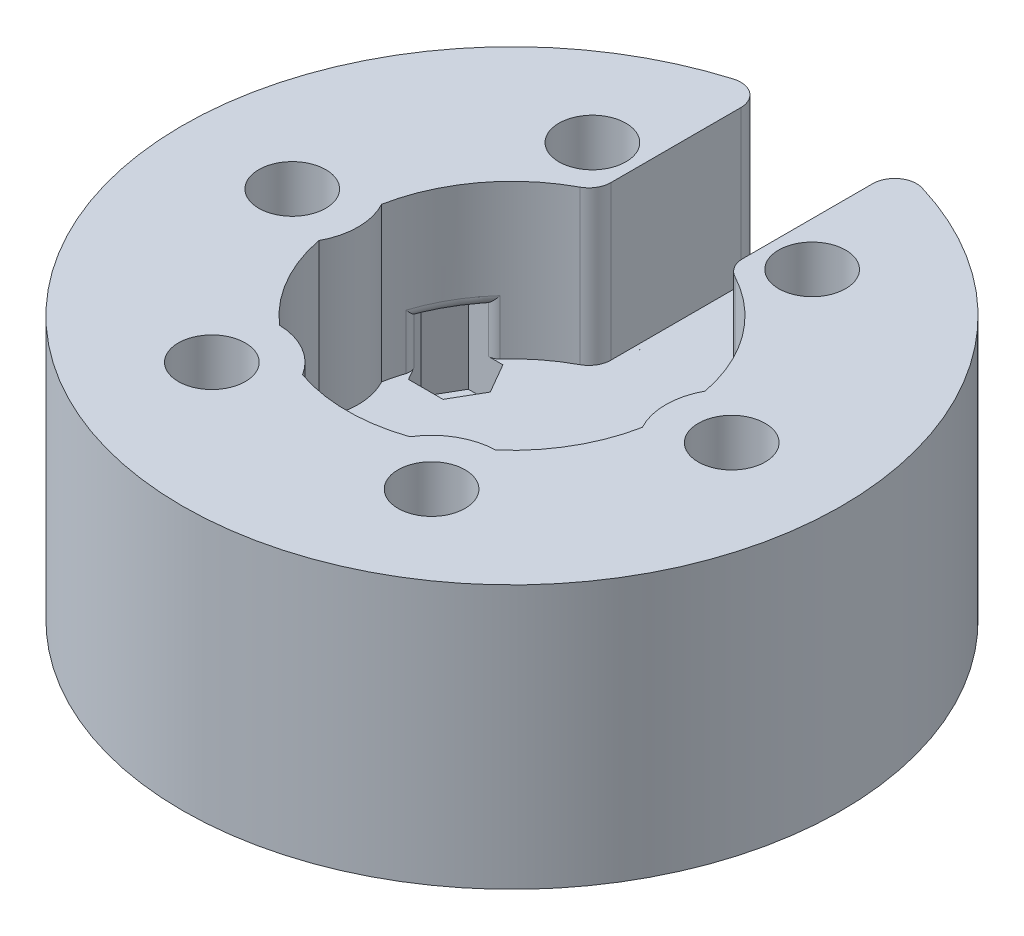
SolidWorks part; units mm, degrees
ref_plane "前视基准面" through (0, 0, 0) normal (0, 0, 1) x (1, 0, 0)
ref_plane "上视基准面" through (0, 0, 0) normal (0, 1, 0) x (1, 0, 0)
ref_plane "右视基准面" through (0, 0, 0) normal (1, 0, 0) x (0, 0, -1)
other "Configuration Table"
sketch "草图1" plane through (0, 0, 0) normal (0, 1, 0) x (1, 0, 0)
  line L0 (-30, 0) -> (30, 0) construction
  line L1 (-6, 0) -> (-3, -5.1962)
  line L2 (-3, -5.1962) -> (3, -5.1962)
  line L3 (3, -5.1962) -> (6, 0)
  line L4 (6, 0) -> (3, 5.1962)
  line L5 (3, 5.1962) -> (-3, 5.1962)
  line L6 (-3, 5.1962) -> (-6, 0)
  line L7 (0, 0) -> (-10, 17.3205) construction
  line L8 (-12.1244, 7) -> (0, 0) construction
  circle A0 centre (0, 0) radius 30
  circle A1 centre (0, 0) radius 5.1962 construction
  circle A2 centre (-10, 17.3205) radius 5.05
  circle A3 centre (10, 17.3205) radius 5.05
  circle A4 centre (20, 0) radius 5.05
  circle A5 centre (10, -17.3205) radius 5.05
  circle A6 centre (-10, -17.3205) radius 5.05
  circle A7 centre (-20, 0) radius 5.05
  circle A8 centre (-10, 17.3205) radius 3.05
  circle A9 centre (10, 17.3205) radius 3.05
  circle A10 centre (20, 0) radius 3.05
  circle A11 centre (10, -17.3205) radius 3.05
  circle A12 centre (-10, -17.3205) radius 3.05
  circle A13 centre (-20, 0) radius 3.05
  circle A14 centre (-12.1244, 7) radius 1.55
  circle A15 centre (12.1244, 7) radius 1.55
  circle A16 centre (0, -14) radius 1.55
  point P26 (0, 0)
  point P38 (0, 0)
  point P39 (4.8677, -12.6024)
  point P40 (0, 0)
  point P44 (0, 0)
  dimension "D1" = 60
  dimension "D3" = 10.1
  dimension "D7" = 6.1
  dimension "D10" = 3.1
  dimension "D2" = 6
  dimension "D4" = 20
  dimension "D5" = 60
  dimension "D9" = 120
  dimension "D11" = 14
  dimension "D12" = 150
  dimension "D6" = 6
  dimension "D8" = 6
  dimension "D13" = 3
extrude "凸台-拉伸3" add sketch "草图1" along normal blind 24 contours A0 A16 A15 A14 A7 A6 A5 A4 A3 A2 L6 L5 L4 L3 L2 L1 | A5 A11 | A4 A10 | A3 A9 | A6 A12 | A7 A13 | A2 A8 | A15 | A14 | A16 region at (-29.1515, 0, 0) region at (-14.9072, 0, -17.3205) region at (5.0928, 0, -17.3205) region at (15.0928, 0, 0) region at (5.0928, 0, 17.3205) region at (-14.9072, 0, 17.3205) region at (-24.9072, 0, 0) region at (-12.1244, 0, -7) region at (12.1244, 0, -7) region at (0, 0, 14)
sketch "草图3" plane through (0, 0, 0) normal (0, -1, 0) x (1, 0, 0)
  line L0 (6, 0) -> (3, -5.1962) construction
  line L1 (3, 5.1962) -> (6, 0) construction
  line L2 (-3, 5.1962) -> (3, 5.1962) construction
  line L3 (-6, 0) -> (-3, 5.1962) construction
  line L4 (-3, -5.1962) -> (-6, 0) construction
  line L5 (3, -5.1962) -> (-3, -5.1962) construction
  line L6 (6, 0) -> (3, -5.1962)
  line L7 (3, 5.1962) -> (6, 0)
  line L8 (-3, 5.1962) -> (3, 5.1962)
  line L9 (-6, 0) -> (-3, 5.1962)
  line L10 (-3, -5.1962) -> (-6, 0)
  line L11 (3, -5.1962) -> (-3, -5.1962)
  circle A0 centre (-20, 0) radius 3.05 construction
  circle A1 centre (-10, 17.3205) radius 3.05 construction
  circle A3 centre (10, 17.3205) radius 3.05 construction
  circle A4 centre (20, 0) radius 3.05 construction
  circle A5 centre (10, -17.3205) radius 3.05 construction
  circle A8 centre (-10, -17.3205) radius 3.05 construction
  circle A9 centre (0, 0) radius 30 construction
  circle A10 centre (-20, 0) radius 3.05
  circle A11 centre (-10, 17.3205) radius 3.05
  circle A13 centre (10, 17.3205) radius 3.05
  circle A14 centre (20, 0) radius 3.05
  circle A15 centre (10, -17.3205) radius 3.05
  circle A18 centre (-10, -17.3205) radius 3.05
  circle A19 centre (0, 0) radius 30
  circle A20 centre (-10, -17.3205) radius 5.05
  circle A21 centre (-20, 0) radius 5.05
  circle A22 centre (-10, 17.3205) radius 5.05
  circle A23 centre (10, 17.3205) radius 5.05
  circle A24 centre (20, 0) radius 5.05
  circle A25 centre (10, -17.3205) radius 5.05
  point P10 (0, 0)
  point P37 (0, 0)
  point P38 (10, -17.3205)
  point P50 (0, 0)
  circle M26 centre (-10, -17.3205) radius 3.05
  circle M27 centre (10, -17.3205) radius 3.05
  circle M28 centre (20, 0) radius 3.05
  circle M29 centre (10, 17.3205) radius 3.05
  circle M30 centre (-10, 17.3205) radius 3.05
  circle M31 centre (-20, 0) radius 3.05
  dimension "D1" = 10.1
  dimension "D2" = 6
extrude "切除-拉伸1" cut sketch "草图3" against normal blind 6 contours A24 M28 | A23 M29 | A22 M30 | A21 M31 | A20 M26 | A25 M27 region at (-14.9072, 0, -17.3205) region at (-24.9072, 0, 0) region at (-14.9072, 0, 17.3205) region at (5.0928, 0, 17.3205) region at (15.0928, 0, 0) region at (5.0928, 0, -17.3205)
sketch "草图5" plane through (0, 0, 0) normal (0, -1, 0) x (1, 0, 0)
  line L0 (-6, 0) -> (-3, 5.1962) construction
  line L1 (-3, -5.1962) -> (-6, 0) construction
  line L2 (3, -5.1962) -> (-3, -5.1962) construction
  line L3 (6, 0) -> (3, -5.1962) construction
  line L4 (3, 5.1962) -> (6, 0) construction
  line L5 (-3, 5.1962) -> (3, 5.1962) construction
  line L6 (-6, 0) -> (-3, 5.1962)
  line L7 (-3, -5.1962) -> (-6, 0)
  line L8 (3, -5.1962) -> (-3, -5.1962)
  line L9 (6, 0) -> (3, -5.1962)
  line L10 (3, 5.1962) -> (6, 0)
  line L11 (-3, 5.1962) -> (3, 5.1962)
extrude "凸台-拉伸4" add sketch "草图5" against normal blind 2 from offset 9 offset against normal yes
sketch "草图8" plane through (0, 24, 0) normal (0, 1, 0) x (1, 0, 0)
  line L0 (10, 17.3205) -> (-10, 17.3205) construction
  line L2 (-6, 2.3205) -> (6, 2.3205)
  line L3 (-6, 2.3205) -> (-6, 32.3205)
  line L4 (-6, 32.3205) -> (6, 32.3205)
  line L5 (6, 2.3205) -> (6, 32.3205)
  line L6 (-6, 2.3205) -> (6, 32.3205) construction
  line L7 (-6, 32.3205) -> (6, 2.3205) construction
  circle A0 centre (0, 0) radius 15
  circle A1 centre (0, 0) radius 30 construction
  circle A2 centre (10, 17.3205) radius 3.05 construction
  circle A3 centre (-10, 17.3205) radius 3.05 construction
  circle A4 centre (0, 0) radius 30
  circle A5 centre (10, 17.3205) radius 3.05
  circle A6 centre (-10, 17.3205) radius 3.05
  circle A7 centre (-20, 0) radius 3.05 construction
  circle A8 centre (-10, -17.3205) radius 3.05 construction
  circle A9 centre (10, -17.3205) radius 3.05 construction
  circle A10 centre (20, 0) radius 3.05 construction
  circle A11 centre (-20, 0) radius 3.05
  circle A12 centre (-10, -17.3205) radius 3.05
  circle A13 centre (10, -17.3205) radius 3.05
  circle A14 centre (20, 0) radius 3.05
  circle A15 centre (-20, 0) radius 6
  circle A16 centre (-10, -17.3205) radius 6
  circle A17 centre (10, -17.3205) radius 6
  circle A18 centre (20, 0) radius 6
  point P11 (0, 17.3205)
  point P29 (0, 0)
  point P30 (0, 0)
  point P32 (0, 0)
  point P36 (0, 0)
  line M13 (-6, 0) -> (-3, 5.1962)
  line M14 (-3, 5.1962) -> (3, 5.1962)
  line M15 (3, 5.1962) -> (6, 0)
  line M16 (6, 0) -> (3, -5.1962)
  line M17 (3, -5.1962) -> (-3, -5.1962)
  line M18 (-3, -5.1962) -> (-6, 0)
  circle M19 centre (0, 0) radius 30
  dimension "D1" = 30
  dimension "D4" = 12
  dimension "D2" = 12
  dimension "D3" = 30
  dimension "D5" = 4
extrude "切除-拉伸5" cut sketch "草图8" against normal blind 14 contours L3 A0 L5 L2 M15 M16 M17 M18 M13 | L2 M13 M18 M17 M16 M15 | L2 M13 M15 M14 | L5 A0 L3 L2 M13 M14 M15 | A0 L5 L3 M19 region at (0, 24, -9.3064) region at (-5.3301, 24, -1.909) region at (0, 24, -3.6545) region at (0, 24, 1.1258) region at (0, 24, -22.1908)
sketch "草图10" plane through (0, 0, 0) normal (0, -1, 0) x (1, 0, 0)
  line L0 (0, 0) -> (-30, 0) construction
  line L1 (0, 14) -> (0, 0)
  circle A0 centre (0, 0) radius 30 construction
  circle A1 centre (0, 14) radius 1.55
  circle A2 centre (12.1244, -7) radius 1.55
  circle A3 centre (-12.1244, -7) radius 1.55
  point P9 (-7.9687, -11.1918)
  point P10 (0, 0)
  point P14 (0, 0)
  dimension "D1" = 3.1
  dimension "D2" = 14
  dimension "D3" = 3
extrude "切除-拉伸7" cut sketch "草图10" against normal up to surface (10 mm away) contours A1 | A3 | A2 region at (1.065, 0, 12.935) region at (12.1244, 0, -7) region at (-12.1244, 0, -7) up to face at (0, 10, -3.1377)
sketch "草图12" plane through (0, 24, 0) normal (0, 1, 0) x (1, 0, 0)
  line L0 (0, 0) -> (-30, 0) construction
  line L1 (-8.9778, 7) -> (-10.5511, 9.725)
  line L2 (-10.5511, 9.725) -> (-13.6976, 9.725)
  line L3 (-13.6976, 9.725) -> (-15.2709, 7)
  line L4 (-15.2709, 7) -> (-13.6976, 4.275)
  line L5 (-13.6976, 4.275) -> (-10.5511, 4.275)
  line L6 (-10.5511, 4.275) -> (-8.9778, 7)
  line L7 (13.6976, 4.275) -> (15.2709, 7)
  line L8 (15.2709, 7) -> (13.6976, 9.725)
  line L9 (13.6976, 9.725) -> (10.5511, 9.725)
  line L10 (10.5511, 9.725) -> (8.9778, 7)
  line L11 (8.9778, 7) -> (10.5511, 4.275)
  line L12 (10.5511, 4.275) -> (13.6976, 4.275)
  line L13 (-3.1466, -14) -> (-1.5733, -16.725)
  line L14 (-1.5733, -16.725) -> (1.5733, -16.725)
  line L15 (1.5733, -16.725) -> (3.1466, -14)
  line L16 (3.1466, -14) -> (1.5733, -11.275)
  line L17 (1.5733, -11.275) -> (-1.5733, -11.275)
  line L18 (-1.5733, -11.275) -> (-3.1466, -14)
  arc A0 (12.3346, 8.5357) -> (13.5594, 6.4142) centre (12.1244, 7) ccw construction
  arc A1 (-13.5594, 6.4142) -> (-12.3346, 8.5357) centre (-12.1244, 7) ccw construction
  arc A2 (1.2248, -14.9499) -> (-1.2248, -14.9499) centre (0, -14) ccw construction
  arc A3 (12.3346, 8.5357) -> (13.5594, 6.4142) centre (12.1244, 7) ccw
  arc A4 (-13.5594, 6.4142) -> (-12.3346, 8.5357) centre (-12.1244, 7) ccw
  arc A5 (1.2248, -14.9499) -> (-1.2248, -14.9499) centre (0, -14) ccw
  circle A6 centre (-12.1244, 7) radius 2.725 construction
  arc A7 (-6, 29.3939) -> (6, 29.3939) centre (0, 0) ccw construction
  point P23 (0, 0)
  point P38 (0, 0)
  arc M26 (-14.725, 2.8591) -> (-6, 13.7477) centre (0, 0) cw
  arc M30 (6, 13.7477) -> (14.725, 2.8591) centre (0, 0) cw
  arc M34 (4.8865, -14.1818) -> (-4.8865, -14.1818) centre (0, 0) cw
  dimension "D1" = 5.45
  dimension "D2" = 3
extrude "切除-拉伸8" cut sketch "草图12" against normal blind 7.5 from offset 10 contours L3 L4 L2 M26 | A4 L4 L5 L6 L1 L2 M26 | A3 L9 L10 L11 L12 L7 M30 | L8 L9 L7 M30 | A5 L15 L16 L17 L18 L13 M34 | L14 L15 L13 M34 region at (-9.8294, 24, -5.675) region at (-13.6367, 24, -7.8732) region at (12.1244, 24, -4.35) region at (13.6367, 24, -7.8732) region at (-2.2968, 24, 12.6739) region at (0, 24, 15.7463) offset against normal yes
fillet "圆角16" radius 2 1 edges at (-6, 17, -13.7477) type face fillet first side face at (-11.7978, 14.5, -8.0299) second side face at (-6, 17, -21.5708)
fillet "圆角17" radius 2 1 edges at (6, 17, -13.7477) type face fillet first side face at (11.7978, 14.5, -8.0299) second side face at (6, 17, -21.5708)
fillet "圆角18" radius 2 1 edges at (-6, 17, -29.3939) type face fillet first side face at (-6, 17, -22.1969) second side face at (0, 0, 30)
fillet "圆角19" radius 2 1 edges at (6, 17, -29.3939) type face fillet first side face at (6, 17, -22.1969) second side face at (0, 0, 30)
fillet "圆角20" radius 1 1 edges at (-14.1323, 12, -5.0278) type face fillet first side face at (-14.3669, 10.1667, -5.4343) second side face at (-12.0332, 14.5, -7.8626)
fillet "圆角21" radius 1 1 edges at (-11.4203, 12, -9.725) type face fillet first side face at (-12.0714, 14.5, -7.7603) second side face at (-11.8897, 10.1667, -9.725)
fillet "圆角23" radius 1 1 edges at (11.4203, 12, -9.725) type face fillet first side face at (12.0332, 14.5, -7.8626) second side face at (11.8897, 10.1667, -9.725)
fillet "圆角24" radius 1 1 edges at (14.1323, 12, -5.0278) type face fillet first side face at (14.3669, 10.1667, -5.4343) second side face at (11.9617, 14.5, -7.9445)
fillet "圆角25" radius 1 1 edges at (2.7119, 12, 14.7528) type face fillet first side face at (0, 14.5, 14.6107) second side face at (2.4773, 10.1667, 15.1593)
fillet "圆角26" radius 1 1 edges at (-2.7119, 12, 14.7528) type face fillet first side face at (0.1076, 14.5, 14.5926) second side face at (-2.4773, 10.1667, 15.1593)
fillet "圆角27" radius 1 1 edges at (12.9904, 14, -7.5) type face fillet first side face at (13.4621, 14, -7.7723) second side face at (12.0002, 14.5, -7.8424)
fillet "圆角28" radius 1 1 edges at (-12.9904, 14, -7.5) type face fillet first side face at (-13.4621, 14, -7.7723) second side face at (-12.0002, 14.5, -7.8424)
fillet "圆角29" radius 1 1 edges at (0, 14, 15) type face fillet first side face at (0, 14, 15.5447) second side face at (0, 14.5, 14.575)
